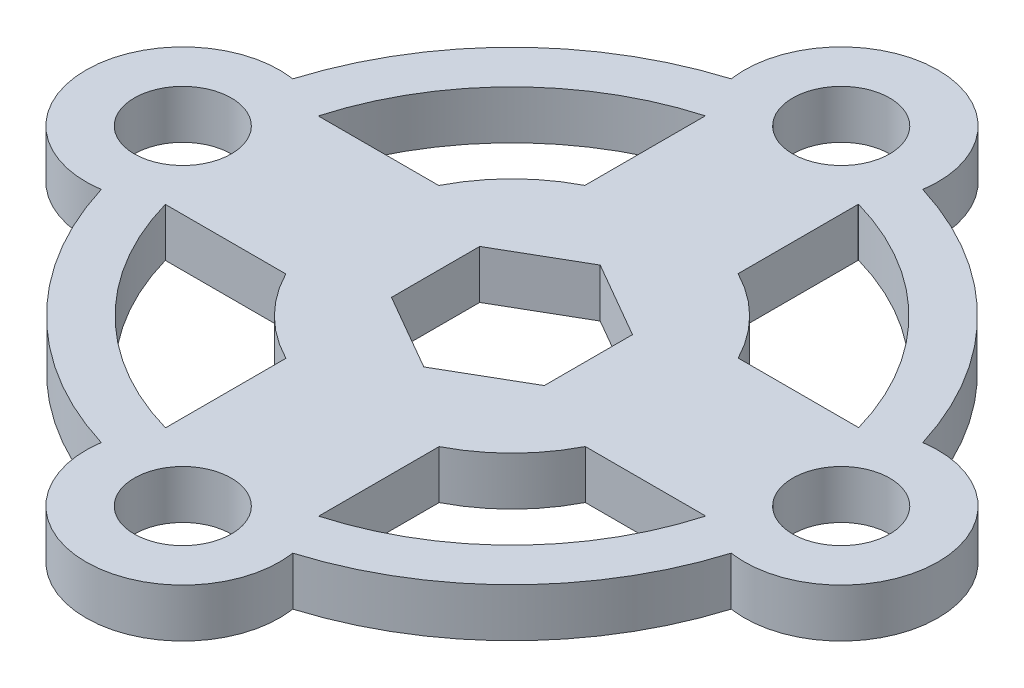
SolidWorks part; units mm, degrees
ref_plane "Front Plane" through (0, 0, 0) normal (0, 0, 1) x (1, 0, 0)
ref_plane "Top Plane" through (0, 0, 0) normal (0, 1, 0) x (1, 0, 0)
ref_plane "Right Plane" through (0, 0, 0) normal (1, 0, 0) x (0, 0, -1)
sketch "Sketch1" plane through (0, 0, 0) normal (0, 1, 0) x (1, 0, 0)
  line L0 (0, 0) -> (5, 0)
  line L1 (0, 5.7735) -> (-5, 2.8868)
  line L2 (-5, 2.8868) -> (-5, -2.8868)
  line L3 (-5, -2.8868) -> (0, -5.7735)
  line L4 (0, -5.7735) -> (5, -2.8868)
  line L5 (5, -2.8868) -> (5, 2.8868)
  line L6 (5, 2.8868) -> (0, 5.7735)
  line L7 (-5.0179, 17.6745) -> (-5.0179, 9.7888)
  line L8 (5, 17.6515) -> (5, 9.798)
  line L9 (17.6745, 5.0179) -> (9.7888, 5.0179)
  line L10 (17.6515, -5) -> (9.798, -5)
  line L11 (5.0179, -17.6745) -> (5.0179, -9.7888)
  line L12 (-5, -17.6515) -> (-5, -9.798)
  line L13 (-17.6745, -5.0179) -> (-9.7888, -5.0179)
  line L14 (-17.6515, 5) -> (-9.798, 5)
  circle A0 centre (0, 0) radius 11
  circle A1 centre (0, 0) radius 5 construction
  circle A2 centre (21.548, 0) radius 3.175
  circle A3 centre (21.548, 0) radius 6.339
  circle A4 centre (0, -21.548) radius 6.339
  circle A5 centre (0, -21.548) radius 3.175
  circle A6 centre (-21.548, 0) radius 6.339
  circle A7 centre (-21.548, 0) radius 3.175
  circle A8 centre (0, 21.548) radius 6.339
  circle A9 centre (0, 21.548) radius 3.175
  arc A10 (-6.2701, 20.6156) -> (-20.6156, 6.2701) centre (0, 0) ccw
  arc A11 (-17.6745, -5.0179) -> (-5.0179, -17.6745) centre (0, 0) ccw
  arc A12 (-20.6156, -6.2701) -> (-6.2701, -20.6156) centre (0, 0) ccw
  arc A13 (20.6156, 6.2701) -> (6.2701, 20.6156) centre (0, 0) ccw
  arc A14 (6.2701, -20.6156) -> (20.6156, -6.2701) centre (0, 0) ccw
  arc A15 (5.0179, -17.6745) -> (17.6745, -5.0179) centre (0, 0) ccw
  arc A16 (17.6745, 5.0179) -> (5.0179, 17.6745) centre (0, 0) ccw
  arc A17 (-5.0179, 17.6745) -> (-17.6745, 5.0179) centre (0, 0) ccw
  point P25 (0, 0)
  point P52 (0, 0)
  dimension "D1" = 21.548
  dimension "D2" = 6.35
  dimension "D3" = 4
  dimension "D4" = 4
extrude "Boss-Extrude1" add sketch "Sketch1" along normal blind 3.175 contours A17 A8 A10 A6 | A6 A7 | A6 A12 A4 A11 | A4 A5 | A6 L13 A0 L14 | A4 L11 A0 L12 | A0 L6 L5 L4 L3 L2 L1 | A8 L7 A0 L8 | A8 A9 | A16 A3 A13 A8 | A3 L9 A0 L10 | A3 A2 | A15 A4 A14 A3 region at (-0.0132, 0, -13.3132) region at (-13.5747, 0, -13.5747) region at (-5.6674, 0, -19.1351) region at (-0.0097, 0, -10.6889) region at (-17.7729, 0, -4.8673) region at (-13.3132, 0, 0.0132) region at (13.5747, 0, -13.5747) region at (13.3132, 0, -0.0132) region at (-13.5747, 0, 13.5747) region at (19.1351, 0, -5.6674) region at (0.0132, 0, 13.3132) region at (-5.6674, 0, 19.1351) region at (13.5747, 0, 13.5747)
